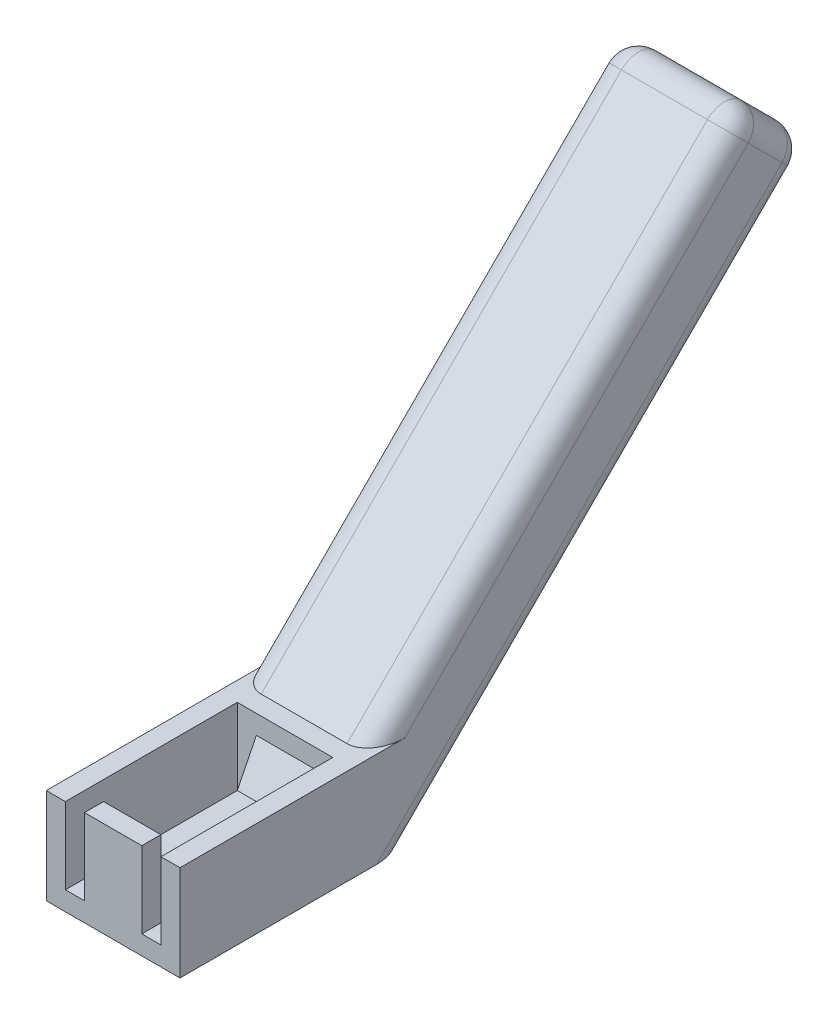
SolidWorks part; units mm, degrees
ref_plane "Front Plane" through (0, 0, 0) normal (0, 0, 1) x (1, 0, 0)
ref_plane "Top Plane" through (0, 0, 0) normal (0, 1, 0) x (1, 0, 0)
ref_plane "Right Plane" through (0, 0, 0) normal (1, 0, 0) x (0, 0, -1)
sketch "Sketch1" plane through (0, 0, 0) normal (1, 0, 0) x (0, 0, -1)
  line L0 (-27.6777, 2.5) -> (-27.6777, 5)
  line L1 (-27.6777, 5) -> (-25.1777, 5)
  line L2 (-25.1777, 5) -> (-27.6777, 10)
  line L3 (-27.6777, 10) -> (-27.6777, 12.5)
  line L4 (-27.6777, 12.5) -> (-30.1777, 12.5)
  line L5 (-30.1777, 12.5) -> (-30.1777, 0)
  line L6 (-30.1777, 0) -> (0, 0)
  line L7 (0, 0) -> (53.033, 53.033)
  line L8 (53.033, 53.033) -> (44.1942, 61.8718)
  line L9 (44.1942, 61.8718) -> (-5.1777, 12.5)
  line L11 (-5.1777, 12.5) -> (-7.6777, 12.5)
  line L12 (-7.6777, 12.5) -> (-7.6777, 10)
  line L14 (-10.1777, 5) -> (-7.6777, 5)
  line L15 (-7.6777, 5) -> (-7.6777, 2.5)
  line L16 (-7.6777, 2.5) -> (-27.6777, 2.5)
  line L18 (-10.1777, 5) -> (-7.6777, 10)
  dimension "D1" = 2.5
  dimension "D2" = 5
  dimension "D3" = 5
  dimension "D4" = 2.5
  dimension "D5" = 2.5
  dimension "D6" = 2.5
  dimension "D7" = 2.5
  dimension "D8" = 2.5
  dimension "D9" = 2.5
  dimension "D10" = 2.5
  dimension "D11" = 2.5
  dimension "D12" = 2.5
  dimension "D13" = 20
  dimension "D14" = 12.5
  dimension "D15" = 12.5
  dimension "D16" = 135
  dimension "D17" = 75
extrude "Boss-Extrude1" add sketch "Sketch1" along normal blind 8.75 and the other way blind 8.75
sketch "Sketch2" plane through (0, 0, 0) normal (0, 0, 1) x (1, 0, 0)
  line L0 (-8.75, 12.5) -> (8.75, 12.5) construction
  line L1 (-8.75, 0) -> (-6.25, 0)
  line L2 (-8.75, 0) -> (-8.75, 12.5)
  line L3 (-8.75, 12.5) -> (-6.25, 12.5)
  line L4 (-6.25, 0) -> (-6.25, 12.5)
  line L6 (8.75, 0) -> (6.25, 0)
  line L7 (8.75, 0) -> (8.75, 12.5)
  line L8 (8.75, 12.5) -> (6.25, 12.5)
  line L9 (6.25, 0) -> (6.25, 12.5)
  dimension "D1" = 2.5
  dimension "D2" = 2.5
extrude "Boss-Extrude2" add sketch "Sketch2" along normal up to surface (30.1777 mm away) up to face at (0, 6.25, 30.1777)
sketch "Sketch3" plane through (0, 0, 0) normal (0, 1, 0) x (1, 0, 0)
  line L1 (-6.25, -30.1777) -> (-3.75, -30.1777)
  line L2 (-6.25, -30.1777) -> (-6.25, -7.6777)
  line L3 (-6.25, -7.6777) -> (-3.75, -7.6777)
  line L4 (-3.75, -30.1777) -> (-3.75, -7.6777)
  line L6 (6.25, -7.6777) -> (3.75, -7.6777)
  line L7 (6.25, -7.6777) -> (6.25, -30.1777)
  line L8 (6.25, -30.1777) -> (3.75, -30.1777)
  line L9 (3.75, -7.6777) -> (3.75, -30.1777)
  line L10 (-8.75, -30.1777) -> (8.75, -30.1777) construction
  point P5 (0, 0)
  point P12 (-6.25, -7.6777)
  point P13 (0, 0)
  point P14 (0, 0)
  point P15 (-5.9449, -29.7945)
  point P16 (0, 0)
  dimension "D1" = 2.5
  dimension "D2" = 2.5
extrude "Cut-Extrude1" cut sketch "Sketch3" along normal through all from surface starting at face at (0, 2.5, 17.6777)
fillet "Fillet1" radius 3.125 8 edges at (0, 61.8718, -44.1942) (8.75, 57.4524, -48.6136) (-8.75, 57.4524, -48.6136) (0, 53.033, -53.033) (8.75, 26.5165, -26.5165) (-8.75, 26.5165, -26.5165) (-8.75, 37.1859, -19.5083) (8.75, 37.1859, -19.5083)
